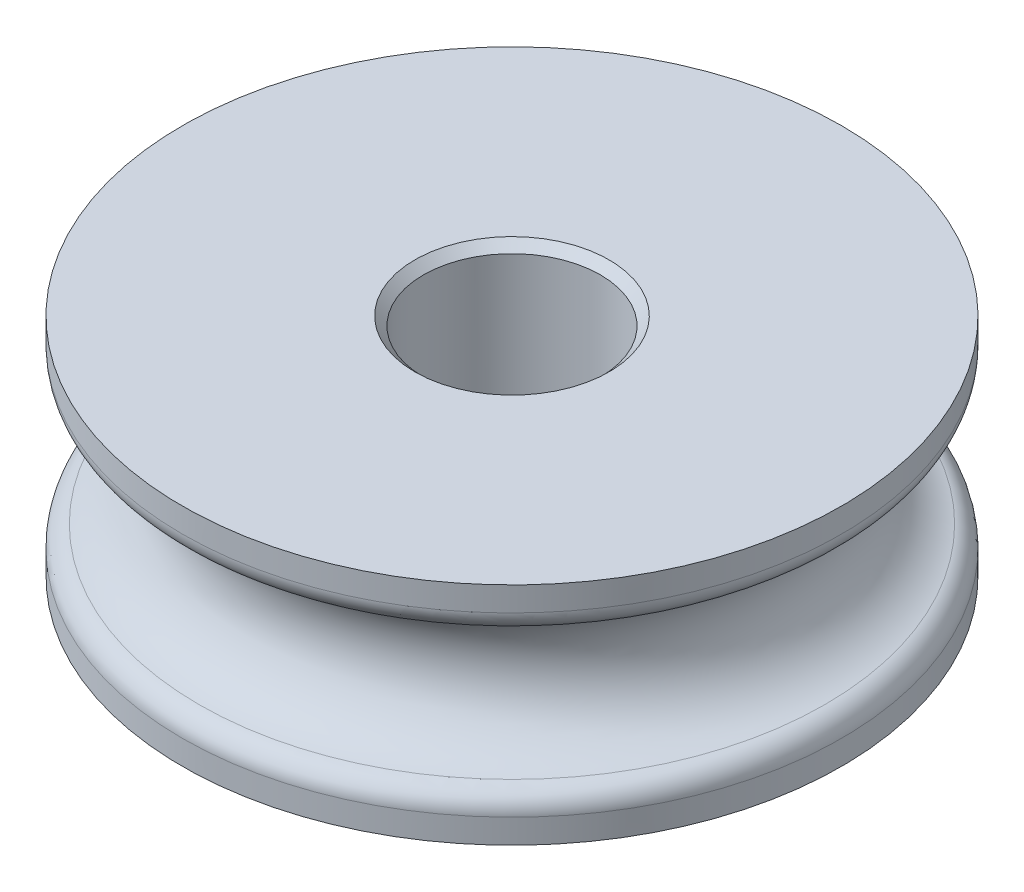
SolidWorks part; units mm, degrees
ref_plane "Front Plane" through (0, 0, 0) normal (0, 0, 1) x (1, 0, 0)
ref_plane "Top Plane" through (0, 0, 0) normal (0, 1, 0) x (1, 0, 0)
ref_plane "Right Plane" through (0, 0, 0) normal (1, 0, 0) x (0, 0, -1)
sketch "Sketch1" plane through (0, 0, 0) normal (1, 0, 0) x (0, 0, -1)
  line L0 (0, 0) -> (24.13, 0)
  line L1 (24.13, 0) -> (24.13, 3.175)
  line L2 (0, 0) -> (0, 16.51)
  line L3 (24.13, 13.335) -> (24.13, 16.51)
  line L4 (24.13, 16.51) -> (0, 16.51)
  arc A2 (24.13, 13.335) -> (24.13, 3.175) centre (24.13, 8.255) ccw
  dimension "D1" = 24.13
  dimension "D2" = 16.51
  dimension "D3" = 3.175
revolve "Revolve1" add sketch "Sketch1" angle 360 about L2
sketch "Sketch2" plane through (0, 0, 0) normal (0, -1, 0) x (1, 0, 0)
  circle A0 centre (0, 0) radius 6.477
  dimension "D1" = 12.954
extrude "Cut-Extrude1" cut sketch "Sketch2" against normal through all
chamfer "Chamfer1" distance 0.635 angle 45 2 edges at (0, 16.51, -6.477) (0, 0, -6.477)
fillet "Fillet1" radius 1.5875 2 edges at (0, 13.335, -24.13) (0, 3.175, -24.13)
